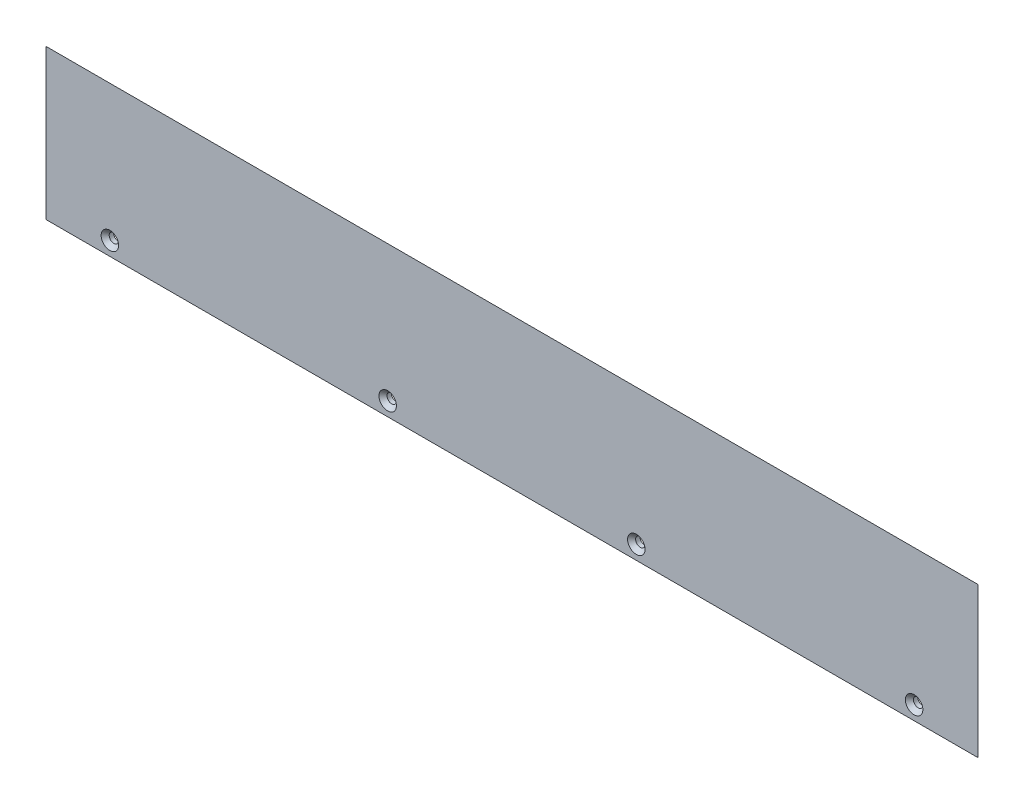
SolidWorks part; units mm, degrees
ref_plane "Front Plane" through (0, 0, 0) normal (0, 0, 1) x (1, 0, 0)
ref_plane "Top Plane" through (0, 0, 0) normal (0, 1, 0) x (1, 0, 0)
ref_plane "Right Plane" through (0, 0, 0) normal (1, 0, 0) x (0, 0, -1)
sketch "Sketch1" plane through (0, 0, 0) normal (0, 0, 1) x (1, 0, 0)
  line L1 (0, 0) -> (335.5, 0)
  line L2 (0, 0) -> (0, 54)
  line L3 (0, 54) -> (335.5, 54)
  line L4 (335.5, 0) -> (335.5, 54)
  dimension "D1" = 54
  dimension "D2" = 335.5
extrude "Boss-Extrude1" add sketch "Sketch1" along normal blind 3
chamfer "Chamfer1" distance 3 angle 45 3 edges at (0, 27, 0) (167.75, 54, 0) (335.5, 27, 0)
sketch "Sketch2" plane through (0, 0, 3) normal (0, 0, 1) x (1, 0, 0)
  line L0 (0, 5) -> (335.5, 5) construction
  line L1 (0, 54) -> (0, 0) construction
  line L2 (335.5, 0) -> (335.5, 54) construction
  line L3 (0, 0) -> (335.5, 0) construction
  circle A0 centre (23, 5) radius 1.5
  circle A1 centre (123, 5) radius 1.5
  circle A2 centre (212.5, 5) radius 1.5
  circle A3 centre (312.5, 5) radius 1.5
  point P18 (25.8658, 2.5381)
  dimension "D6" = 3
  dimension "D1" = 5
  dimension "D2" = 23
  dimension "D3" = 100
  dimension "D4" = 100
  dimension "D5" = 23
hole_wizard "CSK for M3 Flat Head Machine Screw1" positions "Sketch4" profile "Sketch3" countersink size "M3" standard "ANSI Metric" end condition through all
sketch "Sketch4" plane through (0, 0, 3) normal (0, 0, 1) x (1, 0, 0)
  point P0 (23, 5)
  point P3 (123, 5)
  point P6 (212.5, 5)
  point P9 (312.5, 5)
sketch "Sketch3" plane through (23, 5, 3) normal (1, 0, 0) x (0, -1, 0)
  line L0 (0, 0) -> (0, 3)
  line L1 (0, 3) -> (1.7, 3)
  line L2 (1.7, 3) -> (1.7, 1.45)
  line L3 (1.7, 1.45) -> (3.15, 0)
  line L5 (3.15, 0) -> (0, 0)
  line L6 (-1.7, 1.45) -> (-3.15, 0) construction
  line L11 (0, -6.35) -> (0, 107.95) construction
  dimension "Thru Hole Dia." = 3.4
  dimension "Thru Hole Depth" = 3
  dimension "Near C'Sink Dia." = 6.3
  dimension "Near C'Sink Angle" = 90
